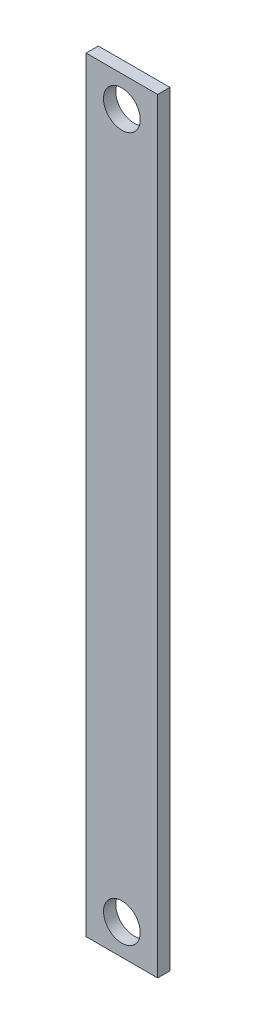
SolidWorks part; units mm, degrees
material "Alloy Steel"
ref_plane "Front Plane" through (0, 0, 0) normal (0, 0, 1) x (1, 0, 0)
ref_plane "Top Plane" through (0, 0, 0) normal (0, 1, 0) x (1, 0, 0)
ref_plane "Right Plane" through (0, 0, 0) normal (1, 0, 0) x (0, 0, -1)
sketch "Sketch1" plane through (0, 0, 0) normal (0, 0, 1) x (1, 0, 0)
  line L1 (-5.85, -62.5) -> (5.85, -62.5)
  line L2 (-5.85, -62.5) -> (-5.85, 62.5)
  line L3 (-5.85, 62.5) -> (5.85, 62.5)
  line L4 (5.85, -62.5) -> (5.85, 62.5)
  line L5 (-5.85, -62.5) -> (5.85, 62.5) construction
  line L6 (-5.85, 62.5) -> (5.85, -62.5) construction
  point P0 (0, 0)
  dimension "D1" = 11.7
  dimension "D2" = 125
extrude "Boss-Extrude1" add sketch "Sketch1" along normal mid plane 2
sketch "Sketch2" plane through (0, 0, 1) normal (0, 0, 1) x (1, 0, 0)
  line L0 (5.85, 62.5) -> (-5.85, 62.5) construction
  line L1 (-5.85, -62.5) -> (5.85, -62.5) construction
  circle A0 centre (0, 57.5) radius 3
  circle A1 centre (0, -57.5) radius 3
  dimension "D3" = 6
  dimension "D4" = 6
  dimension "D1" = 5
  dimension "D2" = 5
extrude "Cut-Extrude1" cut sketch "Sketch2" against normal through all
equation "\"Largeur\"= 11.7"
equation "\"Longueur\"= 125"
equation "\"Epaisseur\"= 2"
equation "\"D2@Sketch1\"=\"Longueur\""
equation "\"D1@Sketch1\"=\"Largeur\""
equation "\"D1@Boss-Extrude1\"=\"Epaisseur\""
equation "\"LargeurPlaqueEpaisse\"= 10mm"
equation "\"D1@Sketch2\"=\"LargeurPlaqueEpaisse\"/2"
equation "\"D2@Sketch2\"=\"LargeurPlaqueEpaisse\"/2"
equation "\"DiametreTrou\"= 6mm"
equation "\"D3@Sketch2\"=\"DiametreTrou\""
equation "\"D4@Sketch2\"=\"DiametreTrou\""
